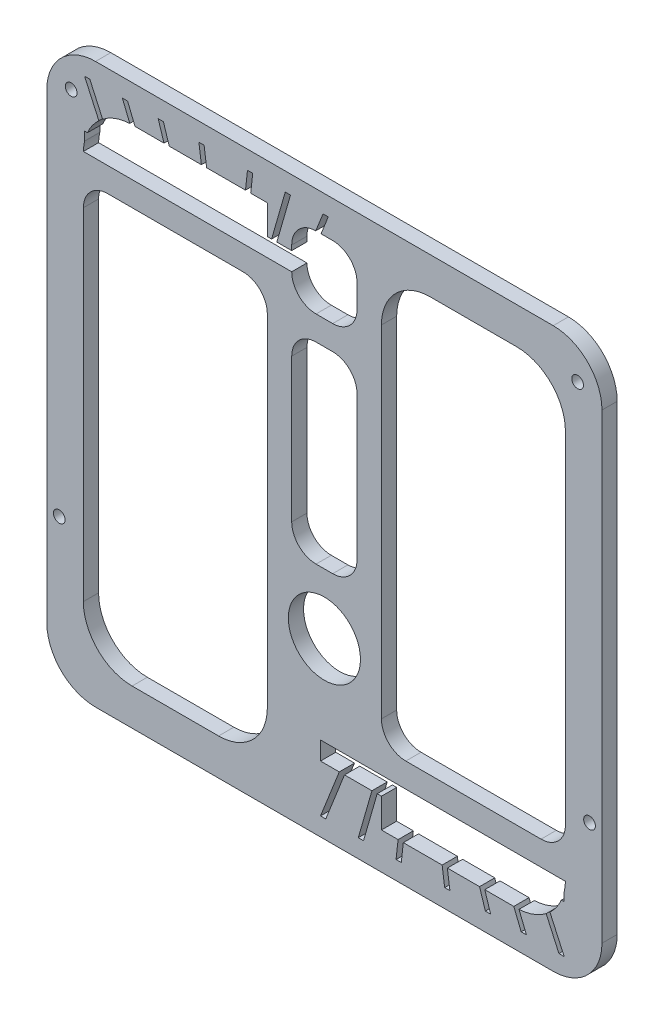
SolidWorks part; units mm, degrees
ref_plane "Front Plane" through (0, 0, 0) normal (0, 0, 1) x (1, 0, 0)
ref_plane "Top Plane" through (0, 0, 0) normal (0, 1, 0) x (1, 0, 0)
ref_plane "Right Plane" through (0, 0, 0) normal (1, 0, 0) x (0, 0, -1)
sketch "Sketch1" plane through (0, 0, 0) normal (0, 0, 1) x (1, 0, 0)
  line L0 (-9.8234, 46.8856) -> (-9.8234, 43.0756) construction
  line L1 (-16.441, -11.4046) -> (41.4264, -11.4046)
  line L2 (-16.441, -11.4046) -> (-16.441, 46.8856)
  line L3 (-16.441, 46.8856) -> (41.4264, 46.8856)
  line L4 (41.4264, -11.4046) -> (41.4264, 46.8856)
  line L6 (-9.8234, 44.9806) -> (-20.2694, 44.9806) construction
  line L7 (-11.9578, 44.9806) -> (-12.504, 44.9806) construction
  line L8 (36.4915, -7.5946) -> (36.4915, -11.4046) construction
  line L10 (-12.631, 43.0756) -> (37.6164, 43.0756)
  line L11 (-12.631, 43.0756) -> (-12.631, -7.5946)
  line L12 (-12.631, -7.5946) -> (37.6164, -7.5946)
  line L13 (37.6164, 43.0756) -> (37.6164, -7.5946)
  line L14 (36.4915, -9.4996) -> (50.994, -9.4996) construction
  line L15 (36.9432, -9.4996) -> (37.4894, -9.4996) construction
  line L16 (37.6164, 41.4945) -> (41.4264, 41.4945) construction
  line L17 (39.5214, 41.4945) -> (39.5214, -21.3698) construction
  line L18 (39.5214, 23.3666) -> (39.5214, 35.6094) construction
  line L19 (-12.631, 40.8837) -> (-16.441, 40.8837) construction
  line L20 (-14.536, 40.8837) -> (-14.536, -26.4843) construction
  line L21 (-14.536, 12.1144) -> (-14.536, -0.1284) construction
  dimension "D1" = 3.81
  dimension "D2" = 3.81
extrude "Boss-Extrude1" add sketch "Sketch1" along normal blind 1.5875
fillet "Fillet3" radius 5.08 4 edges at (37.6164, -7.5946, 0.7937) (-12.631, -7.5946, 0.7937) (37.6164, 43.0756, 0.7937) (-12.631, 43.0756, 0.7937)
sketch "Sketch6" plane through (0, 0, 1.5875) normal (0, 0, 1) x (1, 0, 0)
  line L0 (32.5364, 43.0756) -> (-7.551, 43.0756) construction
  line L1 (-12.631, 37.9956) -> (-12.631, -2.5146) construction
  line L2 (37.6164, -2.5146) -> (37.6164, 37.9956) construction
  line L3 (37.6164, 13.0034) -> (37.6164, 0.405)
  line L4 (18.4394, 43.0756) -> (6.546, 43.0756)
  line L5 (-12.631, 0.405) -> (-12.631, 13.0034)
  line L6 (18.4394, 43.0756) -> (18.4394, -7.5946)
  line L7 (18.4394, -7.5946) -> (6.546, -7.5946)
  line L9 (6.546, 43.0756) -> (6.546, -7.5946)
  line L10 (-7.551, -7.5946) -> (32.5364, -7.5946) construction
  line L11 (8.7335, 6.7042) -> (8.7335, 12.2237) construction
  line L12 (16.2519, 6.7042) -> (16.2519, 13.4807) construction
  line L13 (6.546, 31.0374) -> (6.546, -0.1284) construction
  line L14 (18.4394, 4.4436) -> (18.4394, 35.6094) construction
  circle A0 centre (12.4927, 6.7042) radius 3.7592 construction
  circle A1 centre (12.4927, 6.7042) radius 3.7592
extrude "Boss-Extrude2" add sketch "Sketch6" against normal up to surface (1.5875 mm away) contours L4 L9 L7 L6 A1 region at (12.4927, 18.6182, 1.5875) up to face at (12.4927, 17.7405, 0)
sketch "Sketch4" plane through (0, 0, 1.5875) normal (0, 0, 1) x (1, 0, 0)
  line L6 (18.4394, 35.6094) -> (18.4394, 4.4436) construction
  line L7 (18.4394, 4.4436) -> (37.4894, 4.4436) construction
  line L8 (37.4894, 4.4436) -> (37.4894, 35.6094) construction
  line L9 (-12.504, 40.0276) -> (-12.504, 38.1226) construction
  line L10 (-12.504, 38.1226) -> (12.896, 38.1226) construction
  line L11 (12.896, 38.1226) -> (12.896, 40.0276) construction
  line L12 (12.896, 40.0276) -> (10.9403, 40.0276) construction
  line L13 (10.9403, 40.0276) -> (12.896, 44.9806) construction
  line L14 (12.896, 44.9806) -> (12.3498, 44.9806) construction
  line L15 (12.3498, 44.9806) -> (10.3941, 40.0276) construction
  line L16 (10.3941, 40.0276) -> (7.5365, 40.0276) construction
  line L17 (7.5365, 40.0276) -> (8.959, 44.9806) construction
  line L18 (8.959, 44.9806) -> (8.4128, 44.9806) construction
  line L19 (8.4128, 44.9806) -> (6.9904, 40.0276) construction
  line L20 (6.9904, 40.0276) -> (4.4758, 40.0276) construction
  line L21 (4.4758, 40.0276) -> (5.022, 44.9806) construction
  line L22 (5.022, 44.9806) -> (4.4758, 44.9806) construction
  line L23 (4.4758, 44.9806) -> (3.9297, 40.0276) construction
  line L24 (3.9297, 40.0276) -> (0.6404, 40.0276) construction
  line L25 (0.6404, 40.0276) -> (-0.0452, 44.9806) construction
  line L26 (-0.0452, 44.9806) -> (-0.5914, 44.9806) construction
  line L27 (-0.5914, 44.9806) -> (0.0943, 40.0276) construction
  line L28 (0.0943, 40.0276) -> (-2.7124, 40.0276) construction
  line L29 (-2.7124, 40.0276) -> (-4.287, 44.9806) construction
  line L30 (-4.287, 44.9806) -> (-4.8332, 44.9806) construction
  line L31 (-4.8332, 44.9806) -> (-3.2585, 40.0276) construction
  line L32 (-3.2585, 40.0276) -> (-6.0144, 40.0276) construction
  line L33 (-6.0144, 40.0276) -> (-8.0208, 44.9806) construction
  line L34 (-8.0208, 44.9806) -> (-8.567, 44.9806) construction
  line L35 (-8.567, 44.9806) -> (-6.5605, 40.0276) construction
  line L36 (-6.5605, 40.0276) -> (-9.71, 40.0276) construction
  line L37 (-9.71, 40.0276) -> (-11.9578, 44.9806) construction
  line L38 (-11.9578, 44.9806) -> (-12.504, 44.9806) construction
  line L39 (-12.504, 44.9806) -> (-10.2562, 40.0276) construction
  line L40 (-10.2562, 40.0276) -> (-12.504, 40.0276) construction
  line L47 (18.4394, 35.6094) -> (18.4394, 4.4436)
  line L48 (18.4394, 4.4436) -> (37.4894, 4.4436)
  line L49 (37.4894, 4.4436) -> (37.4894, 35.6094)
  line L50 (-12.504, 40.0276) -> (-12.504, 38.1226)
  line L51 (-12.504, 38.1226) -> (12.896, 38.1226)
  line L52 (12.896, 38.1226) -> (12.896, 40.0276)
  line L53 (12.896, 40.0276) -> (10.9403, 40.0276)
  line L54 (10.9403, 40.0276) -> (12.896, 44.9806)
  line L55 (12.896, 44.9806) -> (12.3498, 44.9806)
  line L56 (12.3498, 44.9806) -> (10.3941, 40.0276)
  line L57 (10.3941, 40.0276) -> (7.5365, 40.0276)
  line L58 (7.5365, 40.0276) -> (8.959, 44.9806)
  line L59 (8.959, 44.9806) -> (8.4128, 44.9806)
  line L60 (8.4128, 44.9806) -> (6.9904, 40.0276)
  line L61 (6.9904, 40.0276) -> (4.4758, 40.0276)
  line L62 (4.4758, 40.0276) -> (5.022, 44.9806)
  line L63 (5.022, 44.9806) -> (4.4758, 44.9806)
  line L64 (4.4758, 44.9806) -> (3.9297, 40.0276)
  line L65 (3.9297, 40.0276) -> (0.6404, 40.0276)
  line L66 (0.6404, 40.0276) -> (-0.0452, 44.9806)
  line L67 (-0.0452, 44.9806) -> (-0.5914, 44.9806)
  line L68 (-0.5914, 44.9806) -> (0.0943, 40.0276)
  line L69 (0.0943, 40.0276) -> (-2.7124, 40.0276)
  line L70 (-2.7124, 40.0276) -> (-4.287, 44.9806)
  line L71 (-4.287, 44.9806) -> (-4.8332, 44.9806)
  line L72 (-4.8332, 44.9806) -> (-3.2585, 40.0276)
  line L73 (-3.2585, 40.0276) -> (-6.0144, 40.0276)
  line L74 (-6.0144, 40.0276) -> (-8.0208, 44.9806)
  line L75 (-8.0208, 44.9806) -> (-8.567, 44.9806)
  line L76 (-8.567, 44.9806) -> (-6.5605, 40.0276)
  line L77 (-6.5605, 40.0276) -> (-9.71, 40.0276)
  line L78 (-9.71, 40.0276) -> (-11.9578, 44.9806)
  line L79 (-11.9578, 44.9806) -> (-12.504, 44.9806)
  line L80 (-12.504, 44.9806) -> (-10.2562, 40.0276)
  line L81 (-10.2562, 40.0276) -> (-12.504, 40.0276)
  line L88 (-14.5106, -1.1684) -> (37.4894, -1.1684)
  line L89 (37.4894, -1.1684) -> (37.4894, -0.1284)
  line L90 (37.4894, -0.1284) -> (6.546, -0.1284)
  line L91 (6.546, -0.1284) -> (-12.504, -0.1284)
  line L92 (-12.504, -0.1284) -> (-14.5106, -0.1284)
  line L93 (-14.5106, -0.1284) -> (-14.5106, -1.1684)
  line L95 (37.4894, -1.1684) -> (37.4894, -0.1284)
  line L114 (37.4894, -4.5466) -> (37.4894, -2.6416)
  line L115 (37.4894, -2.6416) -> (12.0894, -2.6416)
  line L116 (12.0894, -2.6416) -> (12.0894, -4.5466)
  line L117 (12.0894, -4.5466) -> (14.0451, -4.5466)
  line L118 (14.0451, -4.5466) -> (12.0894, -9.4996)
  line L119 (12.0894, -9.4996) -> (12.6356, -9.4996)
  line L120 (12.6356, -9.4996) -> (14.5913, -4.5466)
  line L121 (14.5913, -4.5466) -> (17.4489, -4.5466)
  line L122 (17.4489, -4.5466) -> (16.0264, -9.4996)
  line L123 (16.0264, -9.4996) -> (16.5726, -9.4996)
  line L124 (16.5726, -9.4996) -> (17.995, -4.5466)
  line L125 (17.995, -4.5466) -> (20.5096, -4.5466)
  line L126 (20.5096, -4.5466) -> (19.9634, -9.4996)
  line L127 (19.9634, -9.4996) -> (20.5096, -9.4996)
  line L128 (20.5096, -9.4996) -> (21.0557, -4.5466)
  line L129 (21.0557, -4.5466) -> (24.345, -4.5466)
  line L130 (24.345, -4.5466) -> (25.0306, -9.4996)
  line L131 (25.0306, -9.4996) -> (25.5768, -9.4996)
  line L132 (25.5768, -9.4996) -> (24.8911, -4.5466)
  line L133 (24.8911, -4.5466) -> (27.6978, -4.5466)
  line L134 (27.6978, -4.5466) -> (29.2724, -9.4996)
  line L135 (29.2724, -9.4996) -> (29.8186, -9.4996)
  line L136 (29.8186, -9.4996) -> (28.2439, -4.5466)
  line L137 (28.2439, -4.5466) -> (30.9998, -4.5466)
  line L138 (30.9998, -4.5466) -> (33.0062, -9.4996)
  line L139 (33.0062, -9.4996) -> (33.5524, -9.4996)
  line L140 (33.5524, -9.4996) -> (31.5459, -4.5466)
  line L141 (31.5459, -4.5466) -> (34.6954, -4.5466)
  line L142 (34.6954, -4.5466) -> (36.9432, -9.4996)
  line L143 (36.9432, -9.4996) -> (37.4894, -9.4996)
  line L144 (37.4894, -9.4996) -> (35.2416, -4.5466)
  line L145 (35.2416, -4.5466) -> (37.4894, -4.5466)
  line L146 (37.4894, -4.5466) -> (37.4894, -2.6416)
  line L147 (37.4894, -2.6416) -> (12.0894, -2.6416)
  line L148 (12.0894, -2.6416) -> (12.0894, -4.5466)
  line L149 (12.0894, -4.5466) -> (14.0451, -4.5466)
  line L150 (14.0451, -4.5466) -> (12.0894, -9.4996)
  line L151 (12.0894, -9.4996) -> (12.6356, -9.4996)
  line L152 (12.6356, -9.4996) -> (14.5913, -4.5466)
  line L153 (14.5913, -4.5466) -> (17.4489, -4.5466)
  line L154 (17.4489, -4.5466) -> (16.0264, -9.4996)
  line L155 (16.0264, -9.4996) -> (16.5726, -9.4996)
  line L156 (16.5726, -9.4996) -> (17.995, -4.5466)
  line L157 (17.995, -4.5466) -> (20.5096, -4.5466)
  line L158 (20.5096, -4.5466) -> (19.9634, -9.4996)
  line L159 (19.9634, -9.4996) -> (20.5096, -9.4996)
  line L160 (20.5096, -9.4996) -> (21.0557, -4.5466)
  line L161 (21.0557, -4.5466) -> (24.345, -4.5466)
  line L162 (24.345, -4.5466) -> (25.0306, -9.4996)
  line L163 (25.0306, -9.4996) -> (25.5768, -9.4996)
  line L164 (25.5768, -9.4996) -> (24.8911, -4.5466)
  line L165 (24.8911, -4.5466) -> (27.6978, -4.5466)
  line L166 (27.6978, -4.5466) -> (29.2724, -9.4996)
  line L167 (29.2724, -9.4996) -> (29.8186, -9.4996)
  line L168 (29.8186, -9.4996) -> (28.2439, -4.5466)
  line L169 (28.2439, -4.5466) -> (30.9998, -4.5466)
  line L170 (30.9998, -4.5466) -> (33.0062, -9.4996)
  line L171 (33.0062, -9.4996) -> (33.5524, -9.4996)
  line L172 (33.5524, -9.4996) -> (31.5459, -4.5466)
  line L173 (31.5459, -4.5466) -> (34.6954, -4.5466)
  line L174 (34.6954, -4.5466) -> (36.9432, -9.4996)
  line L175 (36.9432, -9.4996) -> (37.4894, -9.4996)
  line L176 (37.4894, -9.4996) -> (35.2416, -4.5466)
  line L177 (35.2416, -4.5466) -> (37.4894, -4.5466)
  line M210 (6.546, 43.0756) -> (6.546, -7.5946)
  line M212 (18.4394, -7.5946) -> (18.4394, 43.0756)
  arc M223 (-12.631, 37.9956) -> (-7.551, 43.0756) centre (-7.551, 37.9956) cw
  line M224 (-7.551, 43.0756) -> (6.546, 43.0756)
  arc M227 (37.6164, -2.5146) -> (32.5364, -7.5946) centre (32.5364, -2.5146) cw
  dimension "D1" = 0
  dimension "D2" = 0
extrude "Cut-Extrude4" cut sketch "Sketch4" against normal blind 2.54 contours L156 L157 L147 L148 L149 L150 L151 L152 L153 L154 L155 M212 | L159 L160 L158 | L163 L164 L162 | L167 L168 L166 | L171 L172 L170 | L175 L176 L174 | L67 L68 L66 | L63 L64 L62 | L59 L60 L51 L52 L53 L54 L55 L56 L57 L58 M210 | L75 L76 L74 | L79 L80 L78 | L71 L72 L70 M224 | L81 L50 M223 | L177 L146 M227 region at (-12.4098, 39.744, 1.5875) region at (27.7954, -4.405, 1.5875) region at (18.3459, -3.5941, 1.5875) region at (-11.5312, 43.4281, 1.5875) region at (6.6395, 39.0751, 1.5875) region at (-7.908, 44.0277, 1.5875) region at (4.6439, 44.0281, 1.5875) region at (-4.2573, 44.0281, 1.5875) region at (-0.1865, 44.0281, 1.5875) region at (37.3952, -4.2629, 1.5875) region at (36.5166, -7.9471, 1.5875)
sketch "Sketch7" plane through (0, 0, 1.5875) normal (0, 0, 1) x (1, 0, 0)
  line L0 (-12.631, 37.9956) -> (-12.631, -2.5146) construction
  line L1 (-12.631, 38.1226) -> (6.546, 38.1226)
  line L2 (-12.631, 38.1226) -> (-12.631, 35.5826)
  line L3 (-12.631, 35.5826) -> (6.546, 35.5826)
  line L4 (6.546, 38.1226) -> (6.546, 35.5826)
  line L5 (6.546, 38.1226) -> (6.546, -7.5946) construction
  line L9 (37.6164, -2.5146) -> (37.6164, 37.9956) construction
  line L10 (37.6164, -2.6416) -> (18.4394, -2.6416)
  line L11 (37.6164, -2.6416) -> (37.6164, -0.1016)
  line L12 (37.6164, -0.1016) -> (18.4394, -0.1016)
  line L13 (18.4394, -2.6416) -> (18.4394, -0.1016)
  line L14 (18.4394, 43.0756) -> (18.4394, -2.6416) construction
  line L16 (37.4894, -2.6416) -> (12.0894, -2.6416) construction
  line L19 (-12.504, 38.1226) -> (12.896, 38.1226) construction
  dimension "D1" = 2.54
  dimension "D2" = 2.54
extrude "Boss-Extrude3" add sketch "Sketch7" against normal up to surface (1.5875 mm away) up to face at (25.4293, -3.4255, 0)
fillet "Fillet1" radius 5.08 4 edges at (-16.441, -11.4046, 0.7937) (41.4264, -11.4046, 0.7937) (41.4264, 46.8856, 0.7937) (-16.441, 46.8856, 0.7937)
fillet "Fillet4" radius 5.08 2 edges at (6.546, -7.5946, 0.7937) (18.4394, 43.0756, 0.7937)
sketch "Sketch8" plane through (0, 0, 1.5875) normal (0, 0, 1) x (1, 0, 0)
  line L0 (6.546, 35.5826) -> (6.546, -2.5146) construction
  line L1 (9.086, 43.0756) -> (15.8994, 43.0756)
  line L2 (9.086, 43.0756) -> (9.086, 13.0034)
  line L3 (9.086, 13.0034) -> (15.8994, 13.0034)
  line L4 (15.8994, 43.0756) -> (15.8994, 13.0034)
  line L5 (18.4394, 37.9956) -> (18.4394, -0.1016) construction
  line L7 (12.4927, 10.4634) -> (-0.3555, 10.4634) construction
  line L8 (12.4927, 6.7042) -> (12.4927, 10.4634) construction
  line L9 (6.546, 43.0756) -> (4.8119, 43.0756) construction
  line L10 (9.086, 35.5826) -> (15.8994, 35.5826)
  line L11 (-12.631, 35.5826) -> (6.546, 35.5826) construction
  line L12 (9.086, 33.0426) -> (15.8994, 33.0426)
  circle A1 centre (12.4927, 6.7042) radius 3.7592 construction
  dimension "D1" = 2.54
  dimension "D2" = 2.54
  dimension "D3" = 2.54
  dimension "D4" = 2.54
extrude "Cut-Extrude5" cut sketch "Sketch8" against normal up to surface (1.5875 mm away) contours L2 L10 L4 L1 | L12 L2 L3 L4 region at (12.4927, 39.3291, 1.5875) region at (12.4927, 23.023, 1.5875) up to face at (25.2522, -7.214, 0)
fillet "Fillet5" radius 2.54 4 edges at (15.8994, 13.0034, 0.7937) (9.086, 13.0034, 0.7937) (15.8994, 43.0756, 0.7937) (9.086, 43.0756, 0.7937)
fillet "Fillet6" radius 2.54 4 edges at (6.546, 35.5826, 0.7937) (18.4394, -0.1016, 0.7937) (37.6164, -0.1016, 0.7937) (-12.631, 35.5826, 0.7937)
fillet "Fillet7" radius 2.54 4 edges at (15.8994, 35.5826, 0.7937) (15.8994, 33.0426, 0.7937) (9.086, 33.0426, 0.7937) (9.086, 35.5826, 0.7937)
sketch "Sketch9" plane through (0, 0, 1.5875) normal (0, 0, 1) x (1, 0, 0)
  line L0 (-14.536, 12.1144) -> (-14.536, -0.1284) construction
  line L1 (-16.441, 41.8056) -> (-16.441, -6.3246) construction
  line L3 (-14.536, 12.1144) -> (-14.536, -0.1284) construction
  line L4 (-15.7552, 3.9102) -> (-16.441, 3.9102) construction
  line L5 (40.7406, 3.9102) -> (41.4264, 3.9102) construction
  line L6 (36.3464, 46.8856) -> (-11.361, 46.8856) construction
  line L7 (41.4264, -6.3246) -> (41.4264, 41.8056) construction
  circle A0 centre (-13.901, 43.0756) radius 0.6096
  circle A1 centre (38.8864, 43.0756) radius 0.6096
  circle A2 centre (40.131, 3.9102) radius 0.6096
  circle A3 centre (-15.1456, 3.9102) radius 0.6096
  circle A4 centre (-11.1293, 4.4182) radius 0.6096 construction
  circle A5 centre (-11.1293, 4.4182) radius 0.6096 construction
  dimension "D1" = 1.2192
  dimension "D2" = 3.81
  dimension "D3" = 2.54
  dimension "D4" = 2.54
  dimension "D5" = 0.508
extrude "Cut-Extrude6" cut sketch "Sketch9" against normal up to surface (1.5875 mm away) up to face at (12.4927, 23.023, 0)
